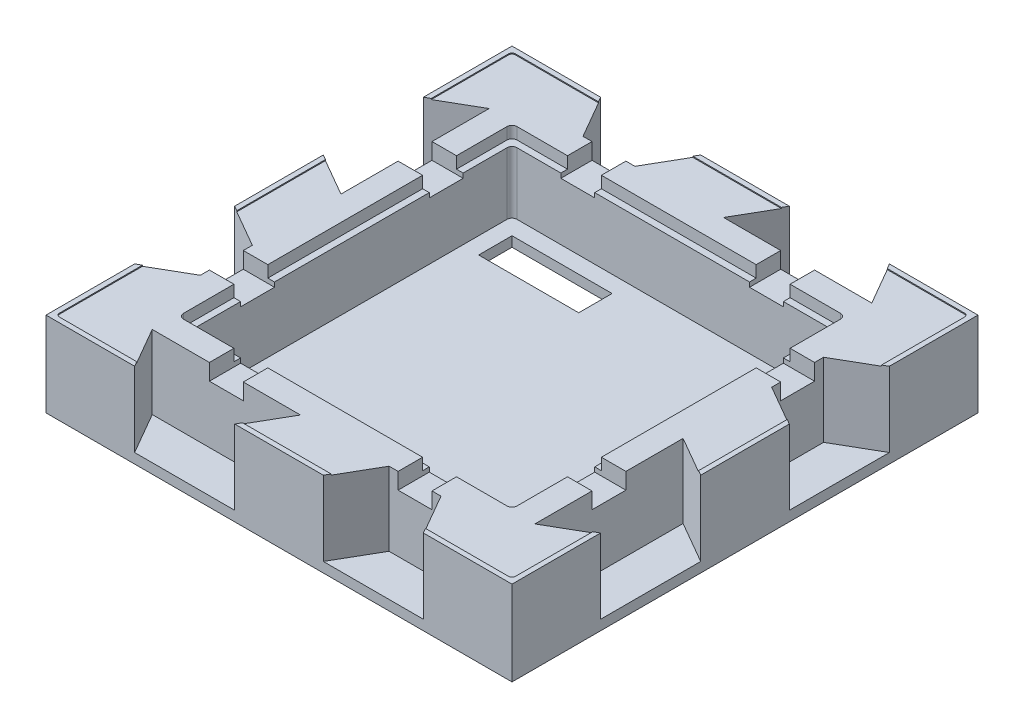
SolidWorks part; units mm, degrees
material "Macor"
ref_plane "Front Plane" through (0, 0, 0) normal (0, 0, 1) x (1, 0, 0)
ref_plane "Top Plane" through (0, 0, 0) normal (0, 1, 0) x (1, 0, 0)
ref_plane "Right Plane" through (0, 0, 0) normal (1, 0, 0) x (0, 0, -1)
sketch "Sketch1" plane through (0, 0, 0) normal (0, 1, 0) x (1, 0, 0)
  line L1 (-69.85, -69.85) -> (69.85, -69.85)
  line L2 (-69.85, -69.85) -> (-69.85, 69.85)
  line L3 (-69.85, 69.85) -> (69.85, 69.85)
  line L4 (69.85, -69.85) -> (69.85, 69.85)
  line L5 (-69.85, -69.85) -> (69.85, 69.85) construction
  line L6 (-69.85, 69.85) -> (69.85, -69.85) construction
  point P0 (0, 0)
  dimension "D1" = 139.7
extrude "Boss-Extrude1" add sketch "Sketch1" along normal mid plane 25.4
sketch "Sketch2" plane through (0, 12.7, 0) normal (0, 1, 0) x (1, 0, 0)
  line L0 (69.85, -69.85) -> (69.85, 69.85) construction
  line L1 (-68.35, -68.35) -> (68.35, -68.35)
  line L2 (-68.35, -68.35) -> (-68.35, 68.35)
  line L3 (-68.35, 68.35) -> (68.35, 68.35)
  line L4 (68.35, -68.35) -> (68.35, 68.35)
  line L5 (-68.35, -68.35) -> (68.35, 68.35) construction
  line L6 (-68.35, 68.35) -> (68.35, -68.35) construction
  point P0 (0, 0)
  dimension "D1" = 1.5
extrude "Cut-Extrude1" cut sketch "Sketch2" against normal offset from surface (0.3 mm away) 0.3 up to face at (0, 12.7, 0)
sketch "Sketch4" plane through (0, 12.7, 0) normal (0, 1, 0) x (1, 0, 0)
  line L0 (-43.2833, -69.85) -> (-50.5002, -57.35)
  line L1 (-69.85, -69.85) -> (69.85, -69.85) construction
  line L2 (-50.5002, -57.35) -> (-6.0665, -57.35)
  line L3 (-6.0665, -57.35) -> (-13.2833, -69.85)
  line L4 (-13.2833, -69.85) -> (-43.2833, -69.85)
  line L5 (43.2833, -69.85) -> (36.0665, -57.35)
  line L24 (43.2833, -69.85) -> (13.2833, -69.85)
  line L25 (-69.85, -69.85) -> (-43.2833, -69.85) construction
  line L26 (-13.2833, -69.85) -> (13.2833, -69.85) construction
  line L27 (43.2833, -69.85) -> (69.85, -69.85) construction
  line L28 (36.0665, -57.35) -> (20.5002, -57.35)
  line L30 (13.2833, -69.85) -> (20.5002, -57.35)
  dimension "D2" = 30
  dimension "D1" = 60
  dimension "D3" = 12.5
  dimension "D4" = 60
extrude "Cut-Extrude2" cut sketch "Sketch4" against normal offset from surface 3 and the other way through all up to face at (0, -12.7, 0)
sketch "Sketch18" plane through (0, 0, 57.35) normal (0, 0, 1) x (1, 0, 0)
  line L1 (0, -13.97) -> (0, 13.97) construction
  line L3 (23.2033, 12.4) -> (23.2033, 7.525)
  line L4 (23.2033, 7.525) -> (33.3633, 7.525)
  line L5 (33.3633, 12.4) -> (33.3633, 7.525)
  line L6 (-23.2033, 12.4) -> (-33.3633, 12.4)
  line L7 (-33.3633, 12.4) -> (-33.3633, 7.525)
  line L8 (-23.2033, 12.4) -> (-23.2033, 7.525)
  line L9 (-23.2033, 7.525) -> (-33.3633, 7.525)
  line L10 (23.2033, 12.4) -> (33.3633, 12.4)
  line L11 (20.5002, 12.4) -> (36.0665, 12.4) construction
  point P7 (28.2833, 12.4)
  point P14 (28.2833, 12.4)
  dimension "D1" = 10.16
  dimension "D2" = 4.875
extrude "Cut-Extrude6" cut sketch "Sketch18" against normal blind 20
ref_axis "Axis1" through (0, 29.6009, 0) along (0, -1, 0)
fillet "Fillet1" radius 1 4 edges at (-68.35, 12.55, 68.35) (68.35, 12.55, 68.35) (68.35, 12.55, -68.35) (-68.35, 12.55, -68.35)
pattern_circular "CirPattern1" count 4 over 360 about axis through (0, 29.6009, 0) along (0, -1, 0) of "Cut-Extrude2", "Cut-Extrude6"
sketch "Sketch19" plane through (0, 12.4, 0) normal (0, 1, 0) x (1, 0, 0)
  line L1 (-50, -50) -> (50, -50)
  line L2 (-50, -50) -> (-50, 50)
  line L3 (-50, 50) -> (50, 50)
  line L4 (50, -50) -> (50, 50)
  line L5 (-50, -50) -> (50, 50) construction
  line L6 (-50, 50) -> (50, -50) construction
  point P0 (0, 0)
  dimension "D1" = 100
extrude "Cut-Extrude8" cut sketch "Sketch19" against normal blind 3.5
sketch "Sketch20" plane through (0, 8.9, 0) normal (0, 1, 0) x (1, 0, 0)
  line L1 (-48, -48) -> (48, -48)
  line L2 (-48, -48) -> (-48, 48)
  line L3 (-48, 48) -> (48, 48)
  line L4 (48, -48) -> (48, 48)
  line L5 (-48, -48) -> (48, 48) construction
  line L6 (-48, 48) -> (48, -48) construction
  point P0 (0, 0)
  dimension "D1" = 96
extrude "Cut-Extrude9" cut sketch "Sketch20" against normal blind 18.6
sketch "Sketch21" plane through (0, -9.7, 0) normal (0, 1, 0) x (1, 0, 0)
  line L0 (-48, 48) -> (-48, -48) construction
  line L1 (-13, 33) -> (-43, 33)
  line L2 (-13, 33) -> (-13, 43)
  line L3 (-13, 43) -> (-43, 43)
  line L4 (-43, 33) -> (-43, 43)
  line L5 (48, 48) -> (-48, 48) construction
  dimension "D1" = 30
  dimension "D2" = 10
  dimension "D3" = 5
  dimension "D4" = 5
extrude "Cut-Extrude10" cut sketch "Sketch21" against normal through all
fillet "Fillet2" radius 1.5 8 edges at (-50, 10.65, -50) (-50, 10.65, 50) (50, 10.65, 50) (50, 10.65, -50) (48, -0.4, 48) (-48, -0.4, 48) (-48, -0.4, -48) (48, -0.4, -48)
sketch "Sketch22" plane through (0, -12.7, 0) normal (0, -1, 0) x (1, 0, 0)
  line L1 (69.85, -69.85) -> (-69.85, -69.85) construction
  line L2 (-69.85, 69.85) -> (-49.85, 69.85)
  line L3 (-69.85, 69.85) -> (-69.85, -69.85)
  line L4 (-69.85, -69.85) -> (-49.85, -69.85)
  line L5 (-49.85, 69.85) -> (-49.85, -69.85)
  line L7 (69.85, 69.85) -> (49.85, 69.85)
  line L8 (69.85, 69.85) -> (69.85, -69.85)
  line L9 (69.85, -69.85) -> (49.85, -69.85)
  line L10 (49.85, 69.85) -> (49.85, -69.85)
  dimension "D1" = 20
split line "Split Line1"
equation "\"panel_width\"= 5.5in"
equation "\"finger_joint_width\"= 30mm"
equation "\"D1@Sketch1\"=\"panel_width\""
equation "\"D2@Sketch4\"=\"finger_joint_width\""
